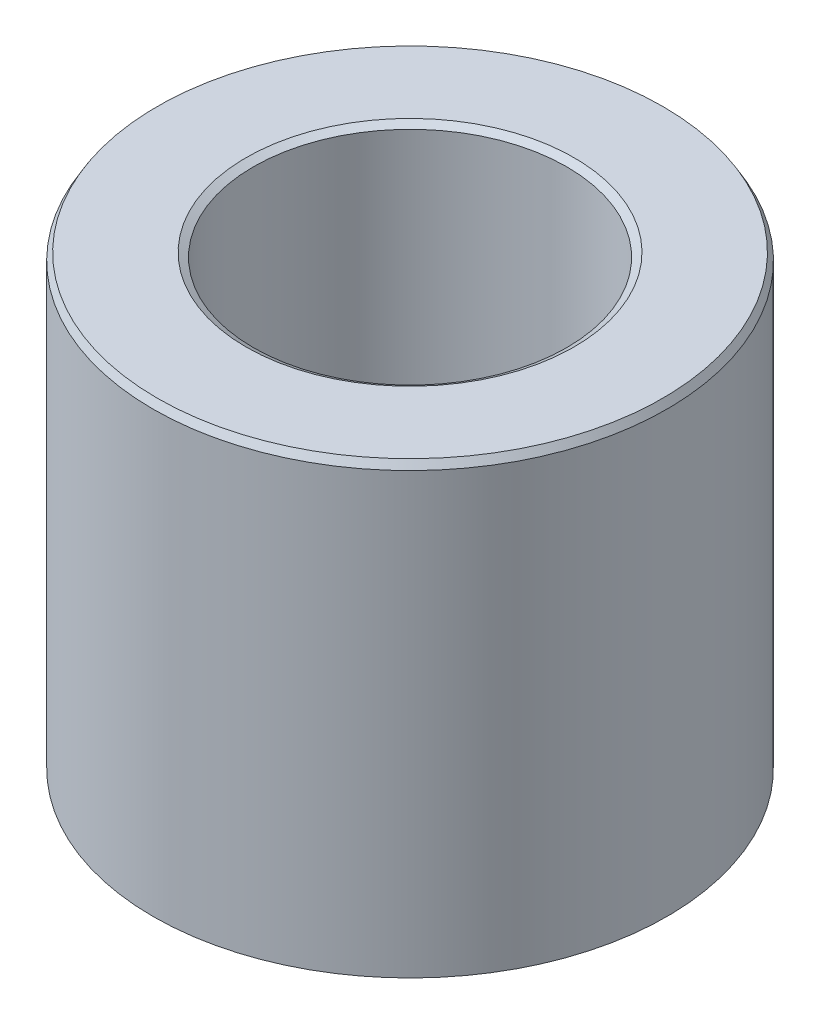
SolidWorks part; units mm, degrees
ref_plane "Front Plane" through (0, 0, 0) normal (0, 0, 1) x (1, 0, 0)
ref_plane "Top Plane" through (0, 0, 0) normal (0, 1, 0) x (1, 0, 0)
ref_plane "Right Plane" through (0, 0, 0) normal (1, 0, 0) x (0, 0, -1)
sketch "Sketch1" plane through (0, 0, 0) normal (0, 1, 0) x (1, 0, 0)
  circle A0 centre (0, 0) radius 57.5
  dimension "SLEEVE_OD" = 115
extrude "Boss-Extrude1" add sketch "Sketch1" along normal blind 100.9141
sketch "Sketch2" plane through (0, 0, 0) normal (0, 1, 0) x (1, 0, 0)
  circle A0 centre (0, 0) radius 35.0602
  dimension "BORE_D" = 70.1204
extrude "Cut-Extrude1" cut sketch "Sketch2" along normal through all
chamfer "Chamfer1" distance 1.6416 angle 30 4 edges at (0, 100.9141, 35.0602) (0, 0, 35.0602) (0, 0, 57.5) (0, 100.9141, 57.5) first distance on face at (0, 100.9141, 35.0602) first distance on face at (0, 0, 35.0602) first distance on face at (0, 100.9141, 57.5)
